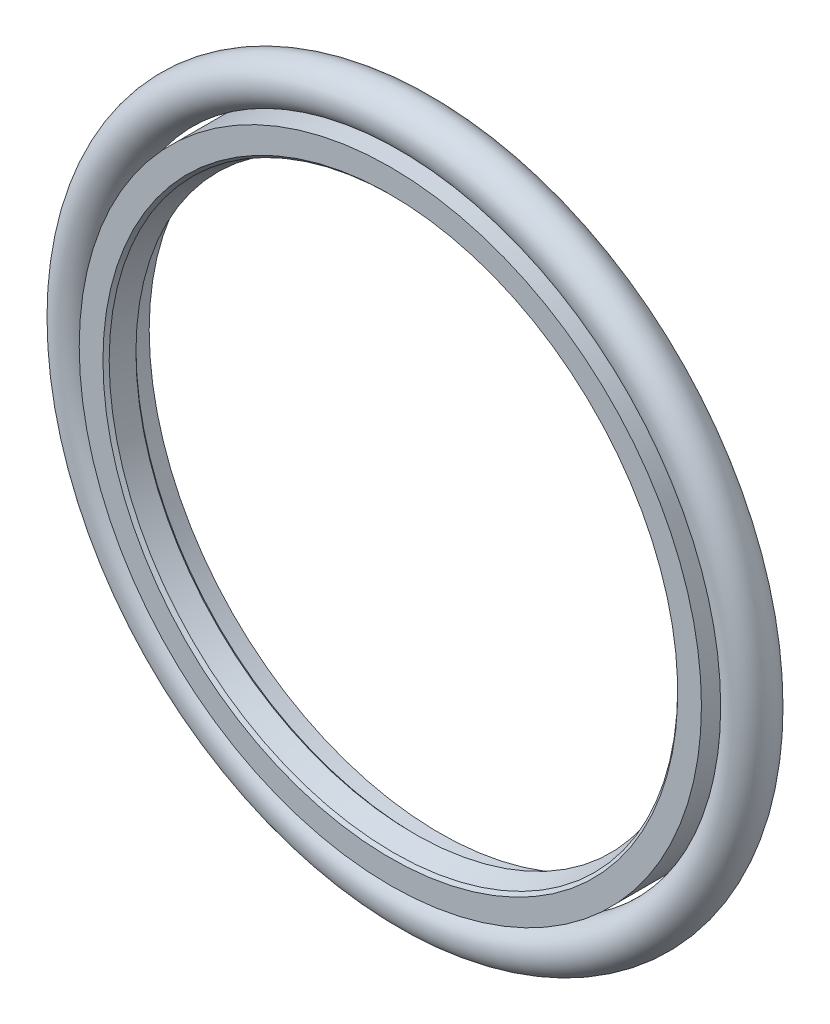
SolidWorks part; units mm, degrees
material "PTFE+NBR"
ref_plane "Front Plane" through (0, 0, 0) normal (0, 0, 1) x (1, 0, 0)
ref_plane "Top Plane" through (0, 0, 0) normal (0, 1, 0) x (1, 0, 0)
ref_plane "Right Plane" through (0, 0, 0) normal (1, 0, 0) x (0, 0, -1)
sketch "Sketch1" plane through (0, 0, 0) normal (1, 0, 0) x (0, 0, -1)
  line L0 (0, 23.25) -> (0, 24.9)
  line L1 (-3.95, 24.9) -> (0, 24.9)
  line L2 (-3.95, 24.9) -> (-3.95, 23)
  line L3 (-1.975, 24.9) -> (-1.975, 56.9493) construction
  line L4 (-3.95, 23) -> (-3.7, 22.7514)
  line L5 (-1.81, 22.5) -> (-1.81, 23)
  line L6 (0, 0) -> (-16.4728, 0) construction
  line L7 (0, 23.25) -> (-1.56, 23.25)
  line L8 (-1.81, 22.5) -> (-2.06, 22.25)
  line L9 (-3.95, 24.9) -> (0, 24.9) construction
  line L11 (-2.06, 22.25) -> (-3.7, 22.7514)
  arc A0 (-1.81, 23) -> (-1.56, 23.25) centre (-1.56, 23) cw
  dimension "D2" = 1.65
  dimension "D4" = 2.65
  dimension "D10" = 0.25
  dimension "D1" = 3.95
  dimension "D3" = 44.5
  dimension "D5" = 1.81
  dimension "D6" = 1.9
  dimension "D7" = 17
  dimension "D8" = 0.25
  dimension "D9" = 0.25
  dimension "D11" = 45
revolve "Revolve1" add sketch "Sketch1" angle 360 about L6
sketch "Sketch4" plane through (0, 0, 0) normal (1, 0, 0) x (0, 0, -1)
  line L0 (0, 0) -> (-3.95, 0) construction
  line L2 (-1.975, 0) -> (-1.975, 52.8756) construction
  line L3 (-3.95, 24.9) -> (-3.95, -24.9) construction
  circle A0 centre (-1.975, 26.96) radius 1.765
  dimension "D1" = 50.39
  dimension "D2" = 3.53
revolve "Revolve2" add sketch "Sketch4" angle 360 about L0
ref_axis "Axis1" through (0, 0, 0) along (0, 0, 1)
